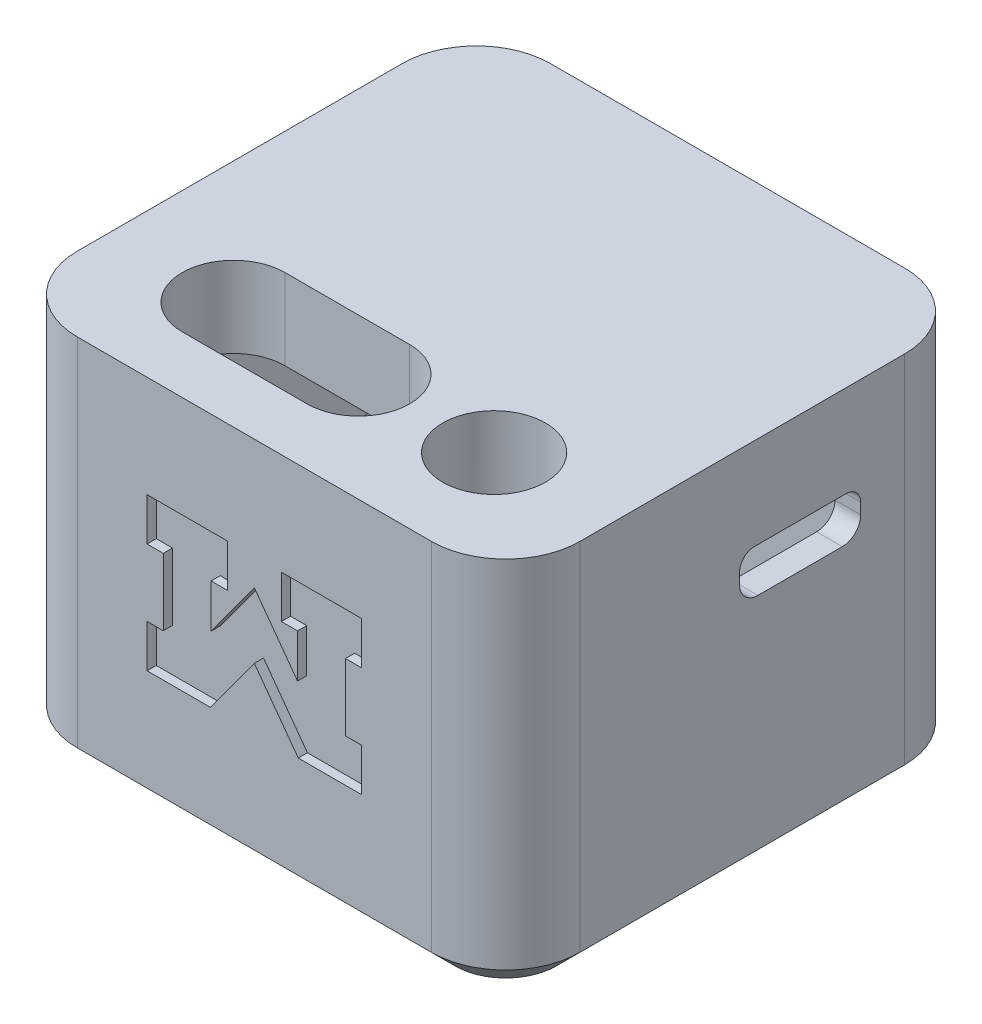
SolidWorks part; units mm, degrees
ref_plane "Front Plane" through (0, 0, 0) normal (0, 0, 1) x (1, 0, 0)
ref_plane "Top Plane" through (0, 0, 0) normal (0, 1, 0) x (1, 0, 0)
ref_plane "Right Plane" through (0, 0, 0) normal (1, 0, 0) x (0, 0, -1)
sketch "Sketch1" plane through (0, 0, 0) normal (0, 1, 0) x (1, 0, 0)
  line L0 (-1.778, 3.3655) -> (-1.778, 25.8445)
  line L1 (3.3655, 0) -> (27.8765, 0)
  line L2 (0, 3.3655) -> (0, 25.8445)
  line L3 (3.3655, 29.21) -> (27.8765, 29.21)
  line L4 (31.242, 3.3655) -> (31.242, 25.8445)
  line L5 (3.3655, 30.988) -> (27.8765, 30.988)
  line L6 (33.02, 3.3655) -> (33.02, 25.8445)
  line L7 (3.3655, -1.778) -> (27.8765, -1.778)
  arc A0 (3.3655, 0) -> (0, 3.3655) centre (3.3655, 3.3655) cw
  arc A1 (0, 25.8445) -> (3.3655, 29.21) centre (3.3655, 25.8445) cw
  arc A2 (27.8765, 29.21) -> (31.242, 25.8445) centre (27.8765, 25.8445) cw
  arc A3 (27.8765, 0) -> (31.242, 3.3655) centre (27.8765, 3.3655) ccw
  arc A4 (-1.778, 25.8445) -> (3.3655, 30.988) centre (3.3655, 25.8445) cw
  arc A5 (27.8765, 30.988) -> (33.02, 25.8445) centre (27.8765, 25.8445) cw
  arc A6 (27.8765, -1.778) -> (33.02, 3.3655) centre (27.8765, 3.3655) ccw
  arc A7 (3.3655, -1.778) -> (-1.778, 3.3655) centre (3.3655, 3.3655) cw
  point P7 (0, 0)
  point P10 (0, 29.21)
  point P13 (31.242, 29.21)
  dimension "D3" = 3.3655
  dimension "D1" = 29.21
  dimension "D2" = 31.242
  dimension "D4" = 1.778
extrude "Boss-Extrude1" add sketch "Sketch1" against normal blind 1.778 contours L7 A6 L6 A5 L5 A4 L0 A7
sketch "Sketch3" plane through (0, -1.778, 0) normal (0, -1, 0) x (1, 0, 0)
  line L4 (0, -3.3655) -> (0, -25.8445)
  line L5 (3.3655, -29.21) -> (27.8765, -29.21)
  line L6 (31.242, -25.8445) -> (31.242, -3.3655)
  line L7 (27.8765, 0) -> (3.3655, 0)
  line L8 (27.8765, 1.778) -> (3.3655, 1.778)
  line L9 (-1.778, -3.3655) -> (-1.778, -25.8445)
  line L10 (3.3655, -30.988) -> (27.8765, -30.988)
  line L11 (33.02, -25.8445) -> (33.02, -3.3655)
  line L12 (27.8765, 1.778) -> (3.3655, 1.778)
  line L13 (-1.778, -3.3655) -> (-1.778, -25.8445)
  line L14 (3.3655, -30.988) -> (27.8765, -30.988)
  line L15 (33.02, -25.8445) -> (33.02, -3.3655)
  arc A4 (0, -25.8445) -> (3.3655, -29.21) centre (3.3655, -25.8445) ccw
  arc A5 (27.8765, -29.21) -> (31.242, -25.8445) centre (27.8765, -25.8445) ccw
  arc A6 (31.242, -3.3655) -> (27.8765, 0) centre (27.8765, -3.3655) ccw
  arc A7 (3.3655, 0) -> (0, -3.3655) centre (3.3655, -3.3655) ccw
  arc A8 (33.02, -3.3655) -> (27.8765, 1.778) centre (27.8765, -3.3655) ccw
  arc A9 (3.3655, 1.778) -> (-1.778, -3.3655) centre (3.3655, -3.3655) ccw
  arc A10 (-1.778, -25.8445) -> (3.3655, -30.988) centre (3.3655, -25.8445) ccw
  arc A11 (27.8765, -30.988) -> (33.02, -25.8445) centre (27.8765, -25.8445) ccw
  arc A12 (33.02, -3.3655) -> (27.8765, 1.778) centre (27.8765, -3.3655) ccw
  arc A13 (3.3655, 1.778) -> (-1.778, -3.3655) centre (3.3655, -3.3655) ccw
  arc A14 (-1.778, -25.8445) -> (3.3655, -30.988) centre (3.3655, -25.8445) ccw
  arc A15 (27.8765, -30.988) -> (33.02, -25.8445) centre (27.8765, -25.8445) ccw
  dimension "D1" = 0
  dimension "D2" = 1.778
extrude "Boss-Extrude2" add sketch "Sketch3" along normal blind 22.86
sketch "Sketch5" plane through (0, 0, 0) normal (0, 1, 0) x (1, 0, 0)
  line L0 (33.02, 25.8445) -> (33.02, 3.3655) construction
  line L1 (18.8849, 2.159) -> (3.1369, 2.159)
  line L2 (3.1369, 5.715) -> (18.8849, 5.715) construction
  line L3 (18.8849, 9.271) -> (3.1369, 9.271)
  line L4 (3.1369, 2.159) -> (3.1369, 9.271)
  line L6 (-1.778, 3.3655) -> (-1.778, 25.8445) construction
  line L8 (18.8849, 9.271) -> (18.8849, 2.159)
  line L16 (3.3655, -1.778) -> (27.8765, -1.778) construction
  circle A0 centre (24.7269, 5.715) radius 3.556
  point P21 (3.1369, 9.271)
  point P24 (18.8849, 9.271)
  dimension "D4" = 21.59
  dimension "D5" = 7.112
  dimension "D1" = 4.9149
  dimension "D2" = 15.748
  dimension "D3" = 7.112
  dimension "D6" = 7.493
  dimension "D7" = 7.493
extrude "Cut-Extrude1" cut sketch "Sketch5" against normal blind 1.778 contours L1 L3 L4 | A0 region at (11.0109, 0, -5.715) region at (24.7269, 0, -5.715)
fillet "Fillet1" radius 3.556 4 edges at (3.1369, -0.889, -2.159) (18.8849, -0.889, -2.159) (18.8849, -0.889, -9.271) (3.1369, -0.889, -9.271)
sketch "Sketch6" plane through (-1.778, 0, 0) normal (-1, 0, 0) x (0, 0, 1)
  line L0 (-30.988, 0) -> (-30.988, -15.0185)
  line L1 (-24.511, -1.778) -> (-11.557, -1.778)
  line L2 (-25.273, -2.54) -> (-25.273, -8.128)
  line L3 (-24.511, -8.89) -> (-11.557, -8.89)
  line L4 (-10.795, -2.54) -> (-10.795, -8.128)
  line L5 (-30.988, -24.638) -> (-30.988, 0) construction
  line L6 (-3.3655, 0) -> (-25.8445, 0) construction
  arc A0 (-11.557, -1.778) -> (-10.795, -2.54) centre (-11.557, -2.54) cw
  arc A1 (-10.795, -8.128) -> (-11.557, -8.89) centre (-11.557, -8.128) cw
  arc A2 (-24.511, -8.89) -> (-25.273, -8.128) centre (-24.511, -8.128) cw
  arc A3 (-24.511, -1.778) -> (-25.273, -2.54) centre (-24.511, -2.54) ccw
  point P13 (-10.795, -1.778)
  point P16 (-10.795, -8.89)
  point P19 (-25.273, -8.89)
  line M7 (-25.8445, 0) -> (-25.8445, -24.638)
  dimension "D5" = 0.762
  dimension "D1" = 14.478
  dimension "D2" = 7.112
  dimension "D3" = 5.715
  dimension "D4" = 1.778
extrude "Cut-Extrude2" cut sketch "Sketch6" against normal blind 12.7 contours A1 L4 A0 L1 L3 M7 | L1 A3 L2 A2 L3 M7 region at (-1.778, -5.334, -18.034)
sketch "Sketch7" plane through (0, 0, -30.988) normal (0, 0, -1) x (-1, 0, 0)
  line L0 (-3.3655, 0) -> (-27.8765, 0) construction
  line L1 (-23.8126, -6.35) -> (-17.4626, -6.35)
  line L2 (-24.8286, -7.366) -> (-24.8286, -8.128)
  line L3 (-23.5586, -9.398) -> (-17.7166, -9.398)
  line L4 (-16.4466, -7.366) -> (-16.4466, -8.128)
  line L5 (-33.02, -24.638) -> (-33.02, 0) construction
  arc A0 (-17.4626, -6.35) -> (-16.4466, -7.366) centre (-17.4626, -7.366) cw
  arc A1 (-23.8126, -6.35) -> (-24.8286, -7.366) centre (-23.8126, -7.366) ccw
  arc A2 (-16.4466, -8.128) -> (-17.7166, -9.398) centre (-17.7166, -8.128) cw
  arc A3 (-23.5586, -9.398) -> (-24.8286, -8.128) centre (-23.5586, -8.128) cw
  point P8 (-16.4466, -6.35)
  point P11 (-24.8286, -6.35)
  point P14 (-16.4466, -9.398)
  dimension "D4" = 1.016
  dimension "D5" = 1.27
  dimension "D1" = 8.382
  dimension "D2" = 3.048
  dimension "D3" = 6.35
  dimension "D6" = 8.1914
extrude "Cut-Extrude3" cut sketch "Sketch7" against normal blind 12.7
sketch3d "3DSketch1"
  line L0 (31.5135, -24.638, -29.4815) -> (31.5135, 0, -29.4815)
  arc A0 (27.8765, -24.638, -30.988) -> (33.02, -24.638, -25.8445) centre (27.8765, -24.638, -25.8445) ccw construction
  arc A1 (27.8765, 0, -30.988) -> (33.02, 0, -25.8445) centre (27.8765, 0, -25.8445) ccw construction
  point P5 (27.8765, -29.7815, -25.8445)
  point P9 (27.8765, -5.1435, -25.8445)
ref_plane "Plane1" through (1.016, 0, 1.016) normal (-0.7071, 0, -0.7071) x (0, 1, 0)
mirror "Mirror1" about plane through (1.016, 0, 1.016) normal (-0.7071, 0, -0.7071) of "Cut-Extrude3"
sketch "Sketch9" plane through (0, -1.778, 0) normal (0, -1, 0) x (1, 0, 0)
  line L8 (6.6929, -10.541) -> (15.3289, -10.541)
  line L9 (15.3289, -0.889) -> (6.6929, -0.889)
  line L10 (6.6929, -9.271) -> (15.3289, -9.271)
  line L11 (15.3289, -2.159) -> (6.6929, -2.159)
  line L12 (6.6929, -9.271) -> (15.3289, -9.271)
  line L13 (15.3289, -2.159) -> (6.6929, -2.159)
  arc A21 (1.8669, -5.715) -> (6.6929, -10.541) centre (6.6929, -5.715) ccw
  circle A22 centre (24.7269, -5.715) radius 3.556
  circle A23 centre (24.7269, -5.715) radius 3.556
  arc A24 (3.1369, -5.715) -> (6.6929, -9.271) centre (6.6929, -5.715) ccw
  arc A25 (15.3289, -9.271) -> (18.8849, -5.715) centre (15.3289, -5.715) ccw
  arc A26 (18.8849, -5.715) -> (15.3289, -2.159) centre (15.3289, -5.715) ccw
  arc A27 (6.6929, -2.159) -> (3.1369, -5.715) centre (6.6929, -5.715) ccw
  arc A28 (3.1369, -5.715) -> (6.6929, -9.271) centre (6.6929, -5.715) ccw
  arc A29 (15.3289, -9.271) -> (18.8849, -5.715) centre (15.3289, -5.715) ccw
  arc A30 (18.8849, -5.715) -> (15.3289, -2.159) centre (15.3289, -5.715) ccw
  arc A31 (6.6929, -2.159) -> (3.1369, -5.715) centre (6.6929, -5.715) ccw
  arc A32 (15.3289, -10.541) -> (20.0279, -6.8149) centre (15.3289, -5.715) ccw
  arc A33 (20.0279, -4.6151) -> (15.3289, -0.889) centre (15.3289, -5.715) ccw
  arc A34 (6.6929, -0.889) -> (1.8669, -5.715) centre (6.6929, -5.715) ccw
  arc A35 (20.0279, -6.8149) -> (20.0279, -4.6151) centre (24.7269, -5.715) ccw
  circle A37 centre (24.7269, -5.715) radius 4.826 construction
  arc A38 (20.1549, -5.715) -> (15.3289, -0.889) centre (15.3289, -5.715) ccw construction
  arc A39 (15.3289, -10.541) -> (20.1549, -5.715) centre (15.3289, -5.715) ccw construction
  point P0 (16.4973, -0.381)
  point P19 (16.4973, -11.049)
  point P20 (16.4973, -5.715)
  point P21 (21.8313, -5.715)
  point P22 (16.4973, -5.715)
  point P23 (25.0063, -5.715)
  point P25 (30.3403, -5.715)
  point P32 (29.8323, -5.715)
  dimension "D1" = 0
  dimension "D2" = 0
  dimension "D3" = 1.27
  dimension "D4" = 1.27
extrude "Boss-Extrude3" add sketch "Sketch9" along normal blind 3.81
ref_plane "Plane2" through (0, 0, -9.652) normal (0, 0, -1) x (-1, 0, 0)
sketch "Sketch11" plane through (0, 0, -9.652) normal (0, 0, -1) x (-1, 0, 0)
  line L0 (1.778, -24.638) -> (0, -24.638)
  line L1 (-3.3655, -24.638) -> (1.778, -24.638) construction
  line L2 (0, -24.638) -> (0.143, -26.273)
  line L3 (0.143, -26.273) -> (1.778, -24.638)
  dimension "D1" = 1.778
  dimension "D2" = 45
  dimension "D3" = 85
sketch "Sketch12" plane through (0, -24.638, 0) normal (0, -1, 0) x (1, 0, 0)
  line L8 (31.242, -25.8445) -> (31.242, -3.3655)
  line L9 (27.8765, 0) -> (3.3655, 0)
  line L10 (0, -3.3655) -> (0, -25.8445)
  line L11 (3.3655, -29.21) -> (27.8765, -29.21)
  line L12 (31.242, -25.8445) -> (31.242, -3.3655)
  line L13 (27.8765, 0) -> (3.3655, 0)
  line L14 (0, -3.3655) -> (0, -25.8445)
  line L15 (3.3655, -29.21) -> (27.8765, -29.21)
  arc A8 (27.8765, -29.21) -> (31.242, -25.8445) centre (27.8765, -25.8445) ccw
  arc A9 (31.242, -3.3655) -> (27.8765, 0) centre (27.8765, -3.3655) ccw
  arc A10 (3.3655, 0) -> (0, -3.3655) centre (3.3655, -3.3655) ccw
  arc A11 (0, -25.8445) -> (3.3655, -29.21) centre (3.3655, -25.8445) ccw
  arc A12 (27.8765, -29.21) -> (31.242, -25.8445) centre (27.8765, -25.8445) ccw
  arc A13 (31.242, -3.3655) -> (27.8765, 0) centre (27.8765, -3.3655) ccw
  arc A14 (3.3655, 0) -> (0, -3.3655) centre (3.3655, -3.3655) ccw
  arc A15 (0, -25.8445) -> (3.3655, -29.21) centre (3.3655, -25.8445) ccw
  dimension "D1" = 0
sweep "Sweep1" add profiles "Sketch11" path "Sketch12"
ref_plane "Plane3" through (0, -19.812, 0) normal (0, -1, 0) x (-1, 0, 0)
sketch "Sketch14" plane through (0, -19.812, 0) normal (0, -1, 0) x (-1, 0, 0)
  line L0 (0, 25.8445) -> (0, 3.3655)
  line L1 (-3.3655, 0) -> (-27.8765, 0)
  line L31 (-13.2822, 29.21) -> (-3.3655, 29.21)
  line L32 (-31.242, 25.8445) -> (-31.242, 3.3655)
  line L33 (-31.242, 11.367) -> (-31.242, 3.3655)
  arc A23 (-31.242, 3.3655) -> (-27.8765, 0) centre (-27.8765, 3.3655) ccw
  arc A24 (-31.242, 3.3655) -> (-27.8765, 0) centre (-27.8765, 3.3655) ccw
  arc A26 (-3.3655, 0) -> (0, 3.3655) centre (-3.3655, 3.3655) ccw
  arc A27 (-3.3655, 0) -> (0, 3.3655) centre (-3.3655, 3.3655) ccw
  arc A29 (0, 25.8445) -> (-3.3655, 29.21) centre (-3.3655, 25.8445) ccw
  arc A30 (0, 25.8445) -> (-3.3655, 29.21) centre (-3.3655, 25.8445) ccw
  dimension "D1" = 8.0015
  dimension "D6" = 9.9167
  dimension "D2" = 0
  dimension "D3" = 0
  dimension "D4" = 0
  dimension "D5" = 0
ref_plane "Plane4" through (13.2822, 0, 0) normal (1, 0, 0) x (0, 0, -1)
sketch "Sketch15" plane through (13.2822, 0, 0) normal (1, 0, 0) x (0, 0, -1)
  line L7 (29.21, -19.812) -> (29.21, -18.034)
  line L8 (29.21, -18.034) -> (28.448, -18.796)
  line L9 (28.448, -18.796) -> (28.448, -19.812)
  line L10 (28.448, -19.812) -> (29.21, -19.812)
  dimension "D1" = 0
  dimension "D4" = 0.762
  dimension "D5" = 1.016
  dimension "D6" = 90
  dimension "D7" = 45
sweep "Sweep2" add profiles "Sketch15" path "Sketch14"
sketch "Sketch16" plane through (0, 0, 1.778) normal (0, 0, 1) x (1, 0, 0)
  line L0 (15.621, -8.9127) -> (15.621, 0) construction
  line L1 (8.197, -7.039) -> (8.197, -17.599) construction
  line L2 (8.197, -12.319) -> (3.3655, -12.319) construction
  line L24 (3.3655, 0) -> (3.3655, -24.638) construction
  line L25 (3.3655, -24.638) -> (27.8765, -24.638) construction
  line L26 (27.8765, -24.638) -> (27.8765, 0) construction
  line L27 (3.3655, 0) -> (27.8765, 0) construction
  line B0 (23.045, -17.599) -> (23.045, -14.639)
  line B1 (23.045, -14.639) -> (21.925, -14.639)
  line B2 (21.925, -14.639) -> (21.925, -9.999)
  line B3 (21.925, -9.999) -> (23.045, -9.999)
  line B4 (23.045, -9.999) -> (23.045, -7.039)
  line B5 (23.045, -7.039) -> (17.493, -7.039)
  line B6 (17.493, -7.039) -> (17.493, -9.999)
  line B7 (17.493, -9.999) -> (18.613, -9.999)
  line B8 (18.613, -9.999) -> (18.613, -13.007)
  line B9 (18.613, -13.007) -> (15.621, -8.9127)
  line B10 (15.621, -13.439) -> (12.581, -17.599)
  line B11 (12.629, -13.007) -> (15.621, -8.9127)
  line B12 (12.581, -17.599) -> (8.197, -17.599)
  line B13 (12.629, -9.999) -> (12.629, -13.007)
  line B14 (13.749, -9.999) -> (12.629, -9.999)
  line B15 (13.749, -7.039) -> (13.749, -9.999)
  line B16 (8.197, -7.039) -> (13.749, -7.039)
  line B17 (8.197, -9.999) -> (8.197, -7.039)
  line B18 (9.317, -9.999) -> (8.197, -9.999)
  line B19 (9.317, -14.639) -> (9.317, -9.999)
  line B20 (8.197, -14.639) -> (9.317, -14.639)
  line B21 (15.621, -13.439) -> (18.661, -17.599)
  line B22 (18.661, -17.599) -> (23.045, -17.599)
  line B23 (8.197, -17.599) -> (8.197, -14.639)
  dimension "D1" = 4.8315
  dimension "D2" = 4.8315
  dimension "D3" = 7.039
  dimension "D4" = 7.039
sketch_block_instance "Block1-1"
sketch_block "Block1"
extrude "Cut-Extrude4" cut sketch "Sketch16" against normal blind 0.635
